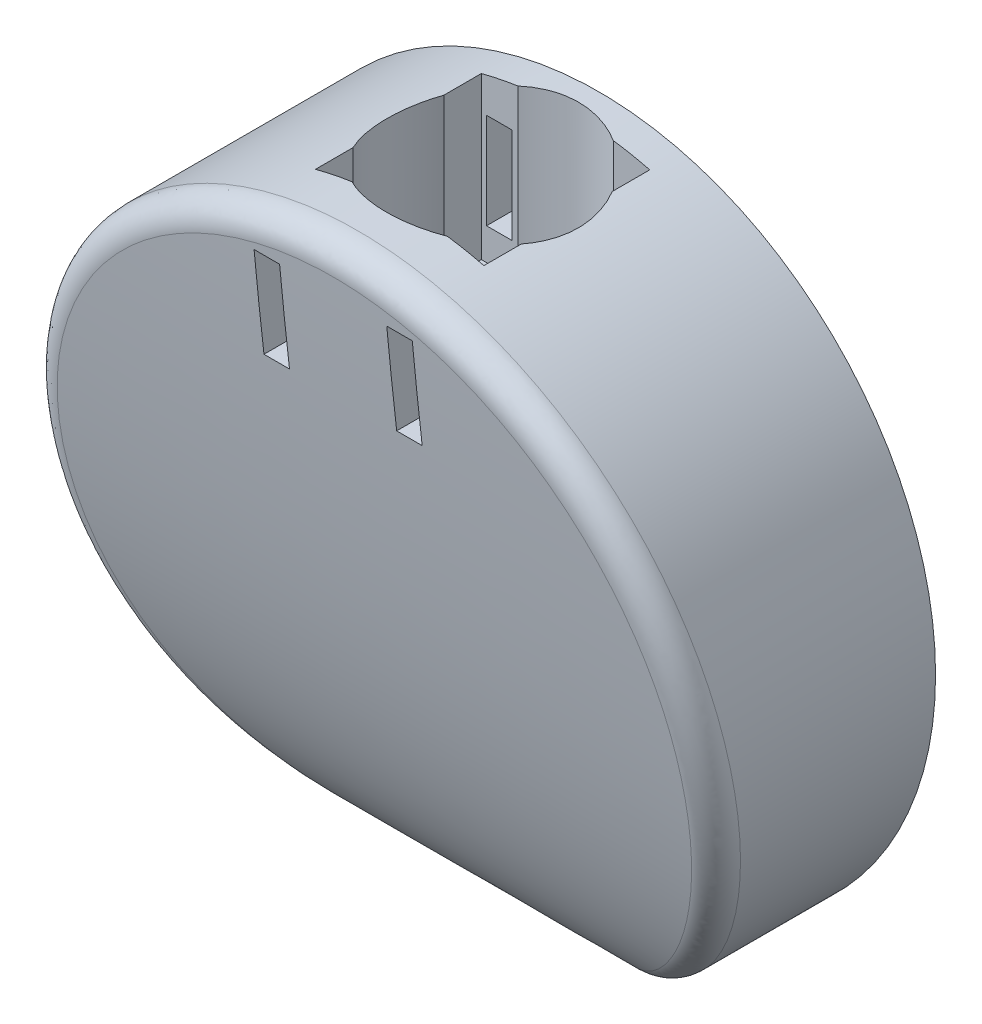
SolidWorks part; units mm, degrees
ref_plane "Plan de face" through (0, 0, 0) normal (0, 0, 1) x (1, 0, 0)
ref_plane "Plan de dessus" through (0, 0, 0) normal (0, 1, 0) x (1, 0, 0)
ref_plane "Plan de droite" through (0, 0, 0) normal (1, 0, 0) x (0, 0, -1)
sketch "Esquisse1" plane through (0, 0, 0) normal (0, 0, 1) x (1, 0, 0)
  circle A0 centre (0.2907, 0.2907) radius 67
  dimension "D1" = 134
extrude "Boss.-Extru.1" add sketch "Esquisse1" along normal blind 53.34
sketch "Esquisse4" plane through (0, 0, 0) normal (1, 0, 0) x (0, 0, -1)
  line L1 (-0.1422, -67.1272) -> (-53.34, -66.7093)
  line L2 (-53.34, -66.7093) -> (-53.34, 67.2907)
  spline S0 degree 3 poles (-53.34, 67.2907) (-53.3149, 64.9653) (-44.6519, -34.8903) (-23.1604, -66.3734) (-0.1422, -67.1272) knots 0 0 0 0 0.36297 1 1 1 1
extrude "Enlèv. mat.-Extru.1" cut sketch "Esquisse4" against normal through all both and the other way through all
fillet "Congé1" radius 5 1 edges at (-0.0427, -66.7085, 4.6747)
ref_plane "Plan2" through (0, 67.2907, 0) normal (0, 1, 0) x (1, 0, 0)
sketch "Esquisse6" plane through (0, 67.2907, 0) normal (0, 1, 0) x (1, 0, 0)
  line L0 (67.2907, 0) -> (-66.7093, 0) construction
  line L1 (-16.7833, -6.35) -> (-9.5231, -6.35)
  line L2 (-16.7833, -6.35) -> (-16.7833, -13.8118)
  line L3 (-16.7833, -39.37) -> (-9.5231, -39.37)
  line L4 (16.7447, -6.35) -> (16.7447, -13.8118)
  line L5 (67.2907, -40.0395) -> (67.2907, 0) construction
  line L6 (-16.7833, -31.9082) -> (-16.7833, -39.37)
  line L7 (9.4845, -39.37) -> (16.7447, -39.37)
  line L8 (16.7447, -31.9082) -> (16.7447, -39.37)
  line L9 (9.4845, -6.35) -> (16.7447, -6.35)
  arc A0 (-16.7833, -13.8118) -> (-16.7833, -31.9082) centre (-0.0193, -22.86) ccw
  arc A1 (-9.5231, -39.37) -> (9.4845, -39.37) centre (-0.0193, -22.86) ccw
  arc A2 (16.7447, -31.9082) -> (16.7447, -13.8118) centre (-0.0193, -22.86) ccw
  arc A3 (9.4845, -6.35) -> (-9.5231, -6.35) centre (-0.0193, -22.86) ccw
  dimension "D5" = 38.1
  dimension "D1" = 33.528
  dimension "D2" = 33.02
  dimension "D3" = 22.86
  dimension "D4" = 67.31
  dimension "D6" = 16.51
  dimension "D7" = 16.764
extrude "Enlèv. mat.-Extru.4" cut sketch "Esquisse6" against normal blind 34.29
ref_plane "Plan4" through (0, 0, 6.35) normal (0, 0, 1) x (1, 0, 0)
sketch "Esquisse10" plane through (0, 0, 6.35) normal (0, 0, 1) x (1, 0, 0)
  line L1 (-15.7461, 58.4007) -> (-10.6661, 58.4007)
  line L2 (-15.7461, 58.4007) -> (-15.7461, 39.3507)
  line L3 (-15.7461, 39.3507) -> (-10.6661, 39.3507)
  line L4 (-10.6661, 58.4007) -> (-10.6661, 39.3507)
  line L5 (-9.5231, 33.0007) -> (-9.5231, 66.5681) construction
  line L7 (-9.5231, 33.0007) -> (-16.7833, 33.0007) construction
  dimension "D1" = 5.08
  dimension "D2" = 19.05
  dimension "D3" = 1.143
  dimension "D4" = 6.35
extrude "Enlèv. mat.-Extru.7" cut sketch "Esquisse10" against normal through all
mirror "Symétrie1" about plane through (0, 0, 0) normal (1, 0, 0) of "Enlèv. mat.-Extru.7"
ref_plane "Plan5" through (0, 0, 22.8591) normal (0, 0, -1) x (-1, 0, 0)
mirror "Symétrie2" about plane through (0, 0, 22.8591) normal (0, 0, -1) of "Symétrie1", "Enlèv. mat.-Extru.7"
sketch "Esquisse12" [suppressed] plane through (15.7461, 0, 0) normal (-1, 0, 0) x (0, 0, 1)
  line L0 (52.6258, 58.4007) -> (50.6529, 39.3507)
  line L1 (50.6529, 39.3507) -> (39.37, 39.3507)
  line L2 (39.37, 39.3507) -> (39.37, 58.4007)
  line L3 (39.37, 58.4007) -> (52.6258, 58.4007)
  line L4 (52.6258, 58.4007) -> (39.37, 58.4007) construction
  line L5 (50.6529, 39.3507) -> (39.37, 39.3507) construction
ref_plane "Plan6" through (0, 35.5407, 0) normal (0, 1, 0) x (1, 0, 0)
sketch "Esquisse7" plane through (0, 35.5407, 0) normal (0, 1, 0) x (1, 0, 0)
  circle A0 centre (-0.0193, -22.86) radius 7.62
  arc A1 (9.4845, -6.35) -> (-9.5231, -6.35) centre (-0.0193, -22.86) ccw construction
  point P13 (-12.1437, -28.924)
  point P14 (-10.4358, -29.8645)
  point P15 (6.6054, -16.2953)
  point P16 (-6.8664, -30.0584)
  point P17 (6.3868, -15.8411)
  point P18 (-6.8721, -16.0049)
  point P19 (-7.2598, -30.0454)
  point P20 (-7.8881, -20.5277)
  point P21 (-6.9265, -14.7316)
  point P22 (6.073, -17.4919)
  point P23 (6.8337, -29.7222)
  dimension "D1" = 15.24
extrude "Enlèv. mat.-Extru.8" cut sketch "Esquisse7" against normal blind 6.35
